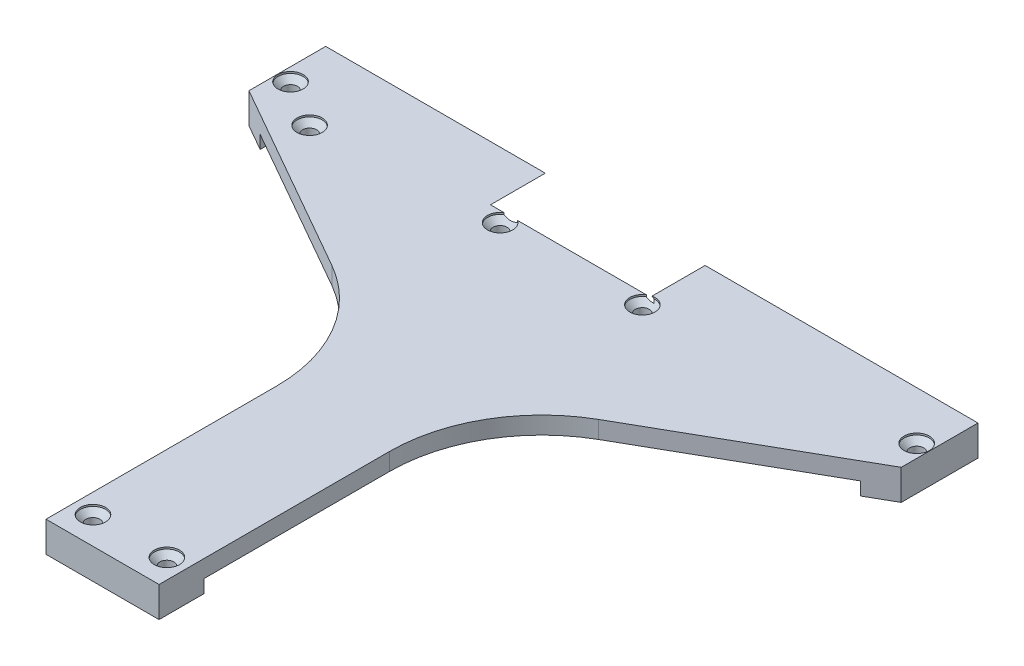
SolidWorks part; units mm, degrees
material "PET"
ref_plane "Plan de face" through (0, 0, 0) normal (0, 0, 1) x (1, 0, 0)
ref_plane "Plan de dessus" through (0, 0, 0) normal (0, 1, 0) x (1, 0, 0)
ref_plane "Plan de droite" through (0, 0, 0) normal (1, 0, 0) x (0, 0, -1)
sketch "Esquisse1" plane through (0, 0, 0) normal (0, 1, 0) x (1, 0, 0)
  line L0 (-13, -127.32) -> (-13, -73.32)
  line L1 (-30.6713, -42.9109) -> (-75, -17.65)
  line L2 (-75, -17.65) -> (-75, 0)
  line L3 (-75, 0) -> (75, 0)
  line L4 (-13, -127.32) -> (13, -127.32)
  line L5 (13, -127.32) -> (13, -73.32)
  line L6 (30.6713, -42.9109) -> (75, -17.65)
  line L7 (75, -17.65) -> (75, 0)
  line L8 (-75, -17.65) -> (-13, -52.9809) construction
  line L9 (-13, -52.9809) -> (-13, -73.32) construction
  line L12 (0, -127.32) -> (0, 0) construction
  arc A0 (-30.6713, -42.9109) -> (-13, -73.32) centre (-48, -73.32) cw
  arc A3 (30.6713, -42.9109) -> (13, -73.32) centre (48, -73.32) ccw
  dimension "D5" = 35
  dimension "D1" = 75
  dimension "D2" = 17.65
  dimension "D3" = 150
  dimension "D4" = 26
  dimension "D6" = 54
  dimension "115.21" = 127.32
extrude "Boss.-Extru.1" add sketch "Esquisse1" along normal blind 4
sketch "Esquisse21" plane through (0, 0, 0) normal (0, -1, 0) x (-1, 0, 0)
  line L0 (75, 0) -> (69, 0)
  line L1 (-75, 0) -> (75, 0) construction
  line L2 (69, 0) -> (69, -21.0691)
  line L3 (75, -17.65) -> (30.6713, -42.9109) construction
  line L4 (69, -21.0691) -> (75, -17.65)
  line L5 (75, -17.65) -> (75, 0)
  line L6 (-75, 0) -> (-69, 0)
  line L7 (-69, 0) -> (-69, -21.0691)
  line L8 (-30.6713, -42.9109) -> (-75, -17.65) construction
  line L9 (-69, -21.0691) -> (-75, -17.65)
  line L10 (-75, -17.65) -> (-75, 0)
  dimension "D1" = 6
  dimension "D2" = 6
extrude "Boss.-Extru.6" add sketch "Esquisse21" along normal blind 3
sketch "Esquisse22" plane through (0, 0, 0) normal (0, -1, 0) x (1, 0, 0)
  line L0 (13, 127.32) -> (13, 73.32) construction
  line L1 (-13, 127.32) -> (13, 127.32)
  line L2 (-13, 127.32) -> (-13, 116.02)
  line L3 (-13, 116.02) -> (13, 116.02)
  line L4 (13, 127.32) -> (13, 116.02)
  dimension "D1" = 11.3
extrude "Boss.-Extru.7" add sketch "Esquisse22" along normal blind 3
hole_wizard "Fraisage pour vis à tête fraisée à 6 pans creux M31" positions "Esquisse5" profile "Esquisse4" countersink size "M3" standard "ISO" end condition up to next
sketch "Esquisse5" plane through (0, 4, 0) normal (0, 1, 0) x (1, 0, 0)
  line L2 (0, 0) -> (0, -127.32) construction
  line L3 (75, 0) -> (-75, 0) construction
  line L4 (-13, -127.32) -> (13, -127.32) construction
  line L5 (-75, 0) -> (-75, -17.65) construction
  line L6 (-13, -120.02) -> (13, -120.02) construction
  line L7 (-13, -73.32) -> (-13, -127.32) construction
  line L8 (13, -127.32) -> (13, -73.32) construction
  point P3 (-19.84, -15.05)
  point P6 (12.87, -15.05)
  point P9 (72, -11.09)
  point P15 (-72, -11.09)
  point P59 (-61.15, -17.55)
  point P72 (-8.5, -120.02)
  point P74 (8.5, -120.02)
  dimension "D2" = 72
  dimension "D3" = 11.09
  dimension "D4" = 72
  dimension "D5" = 19.84
  dimension "D6" = 15.05
  dimension "D7" = 32.71
  dimension "D8" = 17.55
  dimension "D9" = 13.85
  dimension "D10" = 7.3
  dimension "D11" = 17
  dimension "D12" = 8.5
sketch "Esquisse4" plane through (-19.84, 4, 15.05) normal (1, 0, 0) x (0, 0, 1)
  line L0 (0, 0) -> (0, 4)
  line L1 (0, 4) -> (1.6, 4)
  line L2 (1.6, 4) -> (1.6, 1.7)
  line L3 (1.6, 1.7) -> (2.9, 0.4)
  line L4 (2.9, 0.4) -> (2.9, 0)
  line L6 (2.9, 0) -> (0, 0)
  line L7 (-1.6, 1.7) -> (-2.9, 0.4) construction
  line L11 (0, -6.35) -> (0, 107.95) construction
  dimension "Diamètre du perçage jusqu'au prochain" = 3.2
  dimension "Profondeur du perçage jusqu'au prochain" = 4
  dimension "Diamètre du fraisage" = 5.8
  dimension "Angle du fraisage" = 90
  dimension "Dégagement de la tête" = 0.4
sketch "Esquisse16" plane through (0, 0, 0) normal (0, 0, -1) x (-1, 0, 0)
  line L0 (28.5, 0) -> (24.5, 4)
  line L2 (-75, 4) -> (75, 4) construction
  line L3 (24.5, 4) -> (-12.25, 4)
  line L4 (-12.25, 4) -> (-16.25, 0)
  line L5 (-69, 0) -> (69, 0) construction
  line L6 (-16.25, 0) -> (28.5, 0)
  dimension "D1" = 28.5
  dimension "D2" = 16.25
  dimension "D3" = 45
  dimension "D4" = 45
extrude "Enlèv. mat.-Extru.9" cut sketch "Esquisse16" against normal blind 12.6
sketch "Esquisse23" plane through (0, 4, 0) normal (0, 1, 0) x (1, 0, 0)
  line L0 (13, -127.32) -> (13, -73.32) construction
  line L1 (-13, -127.32) -> (13, -127.32)
  line L2 (-13, -127.32) -> (-13, -126.32)
  line L3 (-13, -126.32) -> (13, -126.32)
  line L4 (13, -127.32) -> (13, -126.32)
  dimension "D1" = 1
extrude "Enlèv. mat.-Extru.10" cut sketch "Esquisse23" against normal up to next
